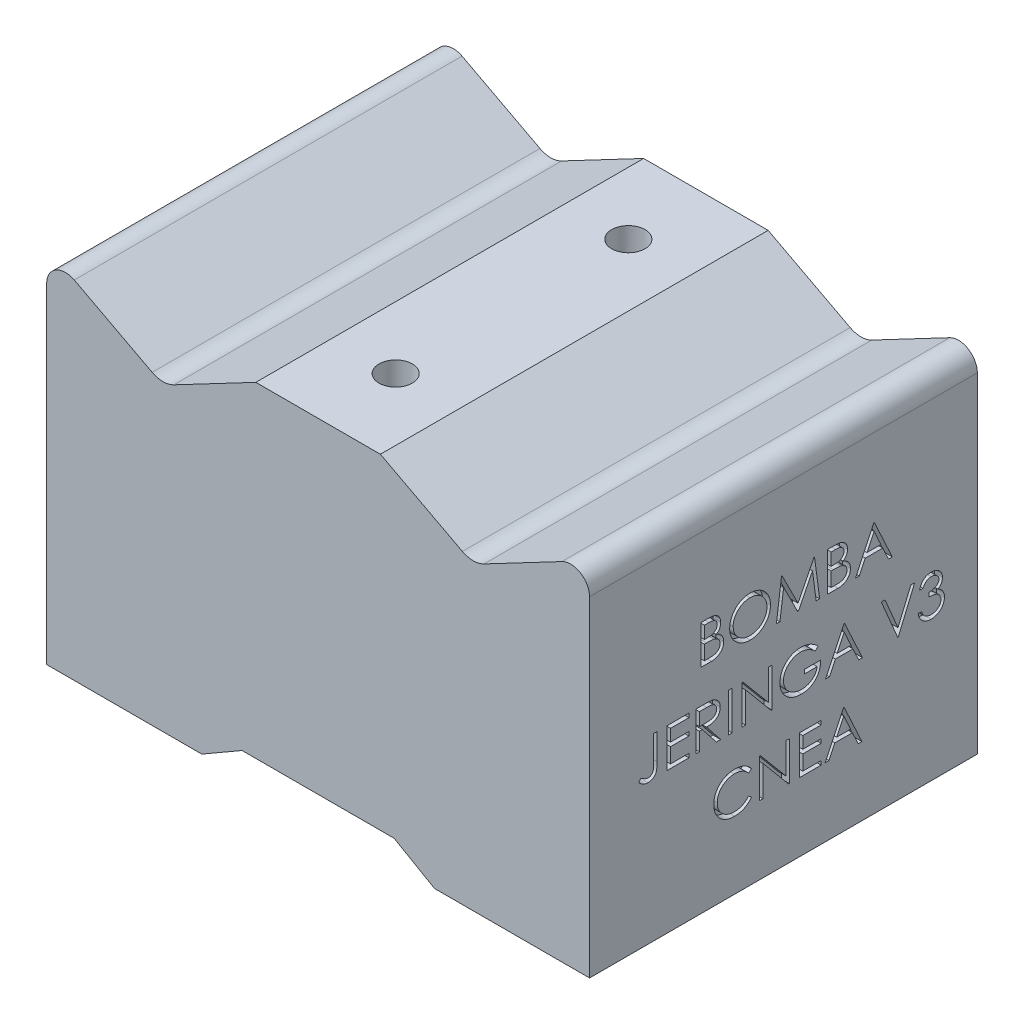
SolidWorks part; units mm, degrees
material "ABS PC"
ref_plane "Front Plane" through (0, 0, 0) normal (0, 0, 1) x (1, 0, 0)
ref_plane "Top Plane" through (0, 0, 0) normal (0, 1, 0) x (1, 0, 0)
ref_plane "Right Plane" through (0, 0, 0) normal (1, 0, 0) x (0, 0, -1)
sketch "Posicion Agujeros" plane through (0, 0, 0) normal (0, 0, 1) x (1, 0, 0)
  line L0 (-18.25, 30) -> (18.25, 30) construction
  line L3 (22, 20) -> (-22, 20) construction
  point P1 (0, 20)
  point P2 (0, 30)
  point P8 (22, 20)
  point P9 (-18.25, 30)
  point P10 (18.25, 30)
  point P18 (-22, 20)
  dimension "D1" = 36.5
  dimension "D2" = 44
  dimension "D3" = 20
  dimension "D4" = 30
  dimension "D5" = 10
sketch "Rodamiento" plane through (0, 0, 0) normal (0, 0, 1) x (1, 0, 0)
  line L0 (6.2877, 18.0537) -> (20.5788, 25.5754)
  line L1 (6.2877, 41.9463) -> (20.5788, 34.4246)
  line L2 (-6.2877, 18.0537) -> (-20.5788, 25.5754)
  line L3 (-20.5788, 34.4246) -> (-6.2877, 41.9463)
  arc A3 (20.5788, 25.5754) -> (20.5788, 34.4246) centre (18.25, 30) ccw
  arc A4 (-20.5788, 25.5754) -> (-20.5788, 34.4246) centre (-18.25, 30) cw
  arc A5 (6.2877, 18.0537) -> (-6.2877, 18.0537) centre (0, 30) cw
  arc A6 (6.2877, 41.9463) -> (-6.2877, 41.9463) centre (0, 30) ccw
  circle A7 centre (-18.25, 30) radius 2.5
  circle A8 centre (18.25, 30) radius 2.5
  arc A9 (-6.2877, 41.9463) -> (-6.2877, 18.0537) centre (0, 30) ccw construction
  dimension "D1" = 13.5
  dimension "D2" = 5
  dimension "D3" = 5
  dimension "D4" = 5
  dimension "D5" = 13.5
  dimension "D6" = 5
sketch "Croquis2" plane through (0, 0, 0) normal (0, 0, 1) x (1, 0, 0)
  line L2 (-35, 45) -> (-35, 0)
  line L3 (-35, 0) -> (-15, 0)
  line L4 (-15, 0) -> (-9.8038, 3)
  line L5 (-9.8038, 3) -> (0, 3)
  line L6 (0, 3) -> (0, 45)
  line L7 (0, 45) -> (-8.0292, 45)
  line L8 (-8.0292, 45) -> (-20, 38.6995)
  line L9 (-20, 38.6995) -> (-31.9708, 45)
  line L10 (-31.9708, 45) -> (-35, 45)
  line L11 (-8.0292, 45) -> (-31.9708, 45) construction
  line L12 (-20, 45) -> (-20, 38.6995) construction
  line L14 (-20.5788, 34.4246) -> (-6.2877, 41.9463) construction
  circle A0 centre (-20, 50) radius 10 construction
  circle A2 centre (-20, 50) radius 13.5134 construction
  dimension "D3" = 20
  dimension "D1" = 20
  dimension "D5" = 35
  dimension "D2" = 27.0267
  dimension "D4" = 20
  dimension "D6" = 3
  dimension "D7" = 20
  dimension "D8" = 30
  dimension "D9" = 3.5134
  dimension "D10" = 45
  dimension "D11" = 6.3005
  dimension "D12" = 124.482
extrude "Saliente-Extruir1" add sketch "Croquis2" along normal blind 25 and the other way blind 25
hole_wizard "Diámetro de taladro Ø8.6 (8.6)1" positions "Croquis20" profile "Croquis21" hole size "Ø8.6" standard "ISO"
sketch "Croquis20" plane through (0, 0, -25) normal (0, 0, -1) x (-1, 0, 0)
  point P0 (22, 20)
sketch "Croquis21" plane through (-22, 20, -25) normal (1, 0, 0) x (0, 1, 0)
  line L0 (0, 0) -> (0, 16.3)
  line L1 (0, 16.3) -> (4.3, 12)
  line L2 (4.3, 12) -> (4.3, 0)
  line L5 (4.3, 0) -> (0, 0)
  line L10 (0, 16.3) -> (-4.3, 12) construction
  line L11 (0, -6.35) -> (0, 107.95) construction
  dimension "Diámetro de taladro" = 8.6
  dimension "Profundidad de taladro" = 12
  dimension "Ángulo de perforador" = 90
fillet "Redondeo1" radius 3 1 edges at (-20, 38.6995, 0)
fillet "Redondeo3" 2 edges at (-35, 45, 0) (-31.9708, 45, 0) type full round first side face at (-35, 22.5, 0) second side face at (-26.684, 42.2174, 0) middle face at (-33.4854, 45, 0)
mirror "Simetría1" about plane through (0, 0, 0) normal (1, 0, 0) of "Redondeo3", "Redondeo1", "Saliente-Extruir1", "Diámetro de taladro Ø8.6 (8.6)1"
sketch "Croquis11" plane through (0, 0, -25) normal (0, 0, -1) x (-1, 0, 0)
  circle A0 centre (0, 30) radius 11
sketch "Croquis13" plane through (0, 0, 0) normal (0, 1, 0) x (1, 0, 0)
  line L1 (25, -15) -> (-25, -15) construction
  line L2 (25, -15) -> (25, 15) construction
  line L3 (25, 15) -> (-25, 15) construction
  line L4 (-25, -15) -> (-25, 15) construction
  line L5 (25, -15) -> (-25, 15) construction
  line L6 (25, 15) -> (-25, -15) construction
  point P5 (25, -15)
  point P6 (25, 15)
  point P7 (-25, 15)
  point P8 (-25, -15)
  dimension "D1" = 30
  dimension "D2" = 50
hole_wizard "Diámetro de taladro Ø5.5 (5.5)1" positions "Croquis14" profile "Croquis15" hole size "Ø5.5" standard "ISO"
sketch "Croquis14" plane through (0, 0, 0) normal (0, -1, 0) x (-1, 0, 0)
  point P0 (25, 15)
sketch "Croquis15" plane through (-25, 0, -15) normal (1, 0, 0) x (0, 0, -1)
  line L0 (0, 0) -> (0, 7)
  line L1 (0, 7) -> (2.75, 7)
  line L2 (2.75, 7) -> (2.75, 0)
  line L5 (2.75, 0) -> (0, 0)
  line L10 (0, 7) -> (-2.75, 7) construction
  line L11 (0, -6.35) -> (0, 107.95) construction
  dimension "Diámetro de taladro" = 5.5
  dimension "Profundidad de taladro" = 7
  dimension "Ángulo de perforador" = 180
pattern_sketch "Matriz de croquis1" of "Diámetro de taladro Ø5.5 (5.5)1" driven by "Croquis13"
hole_wizard "Taladro de margen para M43" positions "Croquis16" profile "Croquis17" hole size "M4" standard "ISO"
sketch "Croquis16" plane through (0, 0, -25) normal (0, 0, -1) x (-1, 0, 0)
  point P0 (-18.25, 30)
  point P3 (18.25, 30)
sketch "Croquis17" plane through (18.25, 30, -25) normal (1, 0, 0) x (0, 1, 0)
  line L0 (0, 0) -> (0, 9.75)
  line L1 (0, 9.75) -> (2.75, 7)
  line L2 (2.75, 7) -> (2.75, 0)
  line L5 (2.75, 0) -> (0, 0)
  line L10 (0, 9.75) -> (-2.75, 7) construction
  line L11 (0, -6.35) -> (0, 107.95) construction
  dimension "Diámetro de taladro" = 5.5
  dimension "Profundidad de taladro" = 7
  dimension "Ángulo de perforador" = 90
sketch "Croquis25" plane through (0, 0, 0) normal (0, 1, 0) x (1, 0, 0)
  line L0 (0, 15) -> (0, -15) construction
  point P4 (0, 15)
  point P5 (0, -15)
  dimension "D1" = 30
hole_wizard "Refrentado para tornillo con cabeza hueca de M41" positions "Croquis26" profile "Croquis27" counterbore size "M4" standard "DIN" end condition through all
sketch "Croquis26" plane through (0, 3, 0) normal (0, -1, 0) x (-1, 0, 0)
  point P0 (0, 15)
  point P3 (0, -15)
sketch "Croquis27" plane through (0, 3, -15) normal (1, 0, 0) x (0, 0, -1)
  line L0 (0, 0) -> (0, 42)
  line L1 (0, 42) -> (2.15, 42)
  line L3 (2.15, 42) -> (2.15, 37.4)
  line L4 (2.15, 37.4) -> (4, 37.4)
  line L5 (4, 37.4) -> (4, 0)
  line L7 (4, 0) -> (0, 0)
  line L11 (0, -6.35) -> (0, 107.95) construction
  dimension "Diámetro de taladro hasta el siguiente" = 4.3
  dimension "Profundidad de taladro hasta el siguiente" = 42
  dimension "Diámetro de refrentado" = 8
  dimension "Profundidad de refrentado" = 37.4
sketch "Croquis28" plane through (35, 0, 0) normal (1, 0, 0) x (0, 0, -1)
  text T0 "    BOMBA \r\nJERINGA V3\r\n     CNEA" font "Century Gothic" height 5
extrude "Cortar-Extruir1" cut sketch "Croquis28" against normal blind 1
